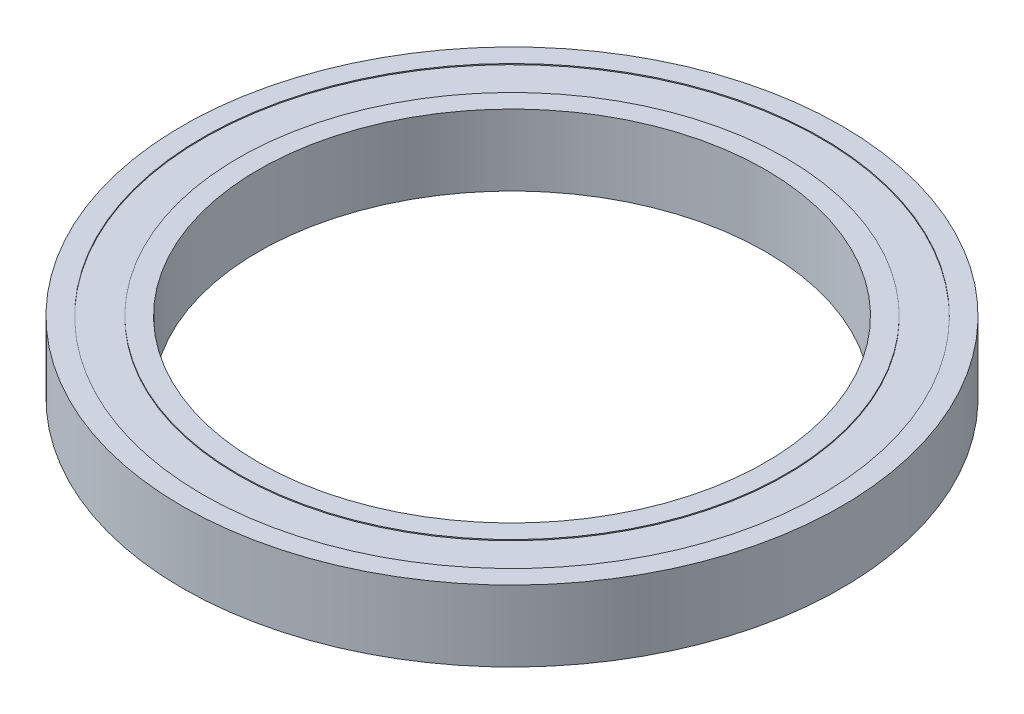
SolidWorks part; units mm, degrees
material "AISI 347 Annealed Stainless Steel (SS)"
ref_plane "Front Plane" through (0, 0, 0) normal (0, 0, 1) x (1, 0, 0)
ref_plane "Top Plane" through (0, 0, 0) normal (0, 1, 0) x (1, 0, 0)
ref_plane "Right Plane" through (0, 0, 0) normal (1, 0, 0) x (0, 0, -1)
sketch "Sketch1" plane through (0, 0, 0) normal (0, 1, 0) x (1, 0, 0)
  circle A0 centre (0, 0) radius 25
  circle A1 centre (0, 0) radius 32.5
  circle A2 centre (0, 0) radius 30.5
  circle A3 centre (0, 0) radius 27
  dimension "D1" = 50
  dimension "D2" = 65
  dimension "D3" = 2
  dimension "D4" = 2
extrude "Boss-Extrude1" add sketch "Sketch1" along normal mid plane 7 contours A1 A2 | A3 A0 region at (-31.5808, 0, 0) region at (-26.2363, 0, 0)
extrude "Boss-Extrude2" add sketch "Sketch1<3>" along normal mid plane 6.8 contours A2 A3 region at (-29.6373, 0, 0)
sketch "Sketch1<3>" plane through (0, 0, 0) normal (0, 1, 0) x (1, 0, 0) same geometry as "Sketch1"
